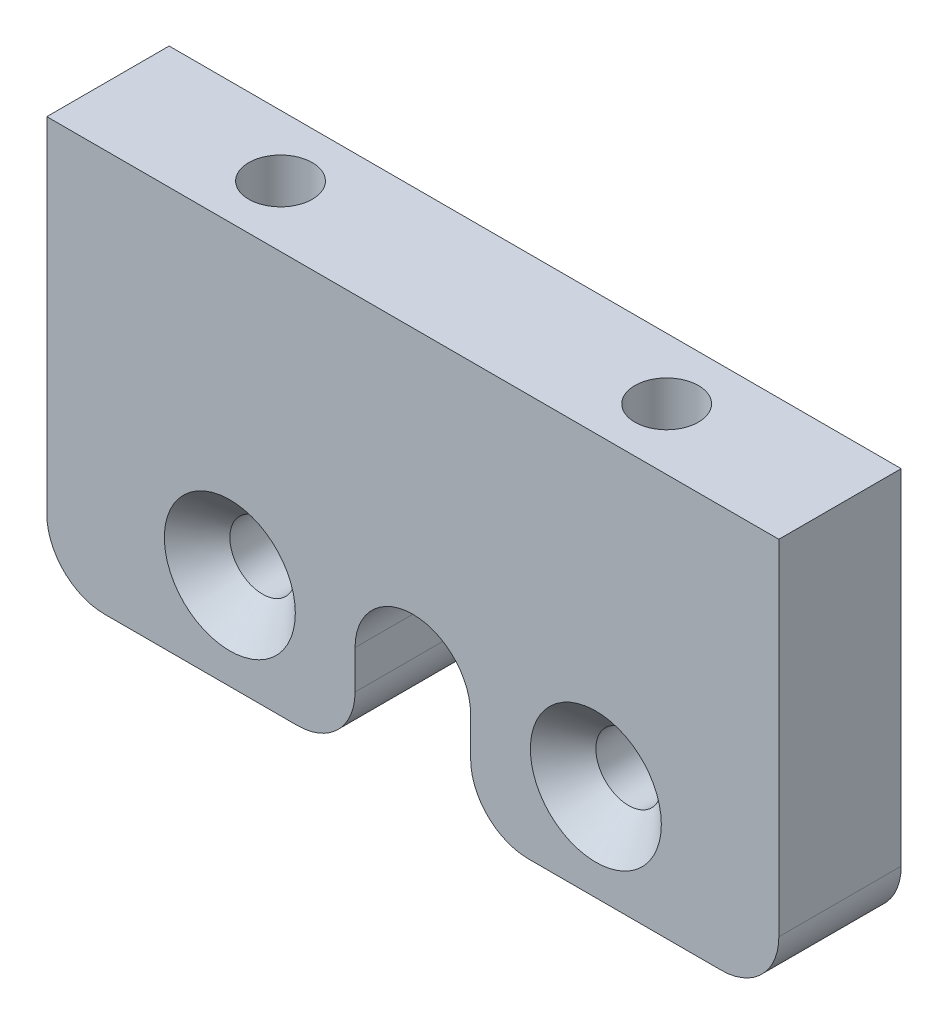
SolidWorks part; units mm, degrees
ref_plane "Front Plane" through (0, 0, 0) normal (0, 0, 1) x (1, 0, 0)
ref_plane "Top Plane" through (0, 0, 0) normal (0, 1, 0) x (1, 0, 0)
ref_plane "Right Plane" through (0, 0, 0) normal (1, 0, 0) x (0, 0, -1)
sketch "Sketch1" plane through (0, 0, -33.2537) normal (0, 0, 1) x (1, 0, 0)
  line L0 (-5.0687, 6.9987) -> (0.5439, 6.9987) construction
  line L1 (3, 6.9987) -> (3, 1.9987)
  line L2 (-3, 6.9987) -> (-3, 1.9987)
  line L3 (3, 1.9987) -> (19, 1.9987)
  line L4 (-3, 1.9987) -> (-19, 1.9987)
  line L5 (19, 1.9987) -> (19, 22.8687)
  line L6 (19, 22.8687) -> (-19, 22.8687)
  line L7 (-19, 22.8687) -> (-19, 1.9987)
  circle A0 centre (0, 6.9987) radius 9.5 construction
  circle A1 centre (9.5, 6.9987) radius 1.7
  circle A2 centre (-9.5, 6.9987) radius 1.7
  arc A4 (3, 6.9987) -> (-3, 6.9987) centre (0, 6.9987) ccw
extrude "Boss-Extrude1" add sketch "Sketch1" along normal blind 6.35
chamfer "Chamfer1" distance 1.7 angle 45 2 edges at (-7.8, 6.9987, -26.9037) (11.2, 6.9987, -26.9037)
sketch "Sketch2" plane through (0, 22.8687, 0) normal (0, 1, 0) x (1, 0, 0)
  line L0 (19, 30.0787) -> (13.1436, 30.0787) construction
  line L2 (0, 26.9037) -> (0, 22.3463) construction
  line L4 (-10, 26.9037) -> (-10, 22.3463) construction
  line L5 (10, 26.9037) -> (10, 22.3463) construction
  circle A0 centre (10, 30.0787) radius 1.65
  circle A1 centre (-10.0429, 30.0787) radius 1.65
  dimension "D3" = 3.3
  dimension "D4" = 3.3
  dimension "D1" = 10
  dimension "D2" = 10
extrude "Cut-Extrude1" cut sketch "Sketch2" against normal blind 10
fillet "Fillet1" radius 3 4 edges at (-19, 1.9987, -30.0787) (-3, 1.9987, -30.0787) (3, 1.9987, -30.0787) (19, 1.9987, -30.0787)
